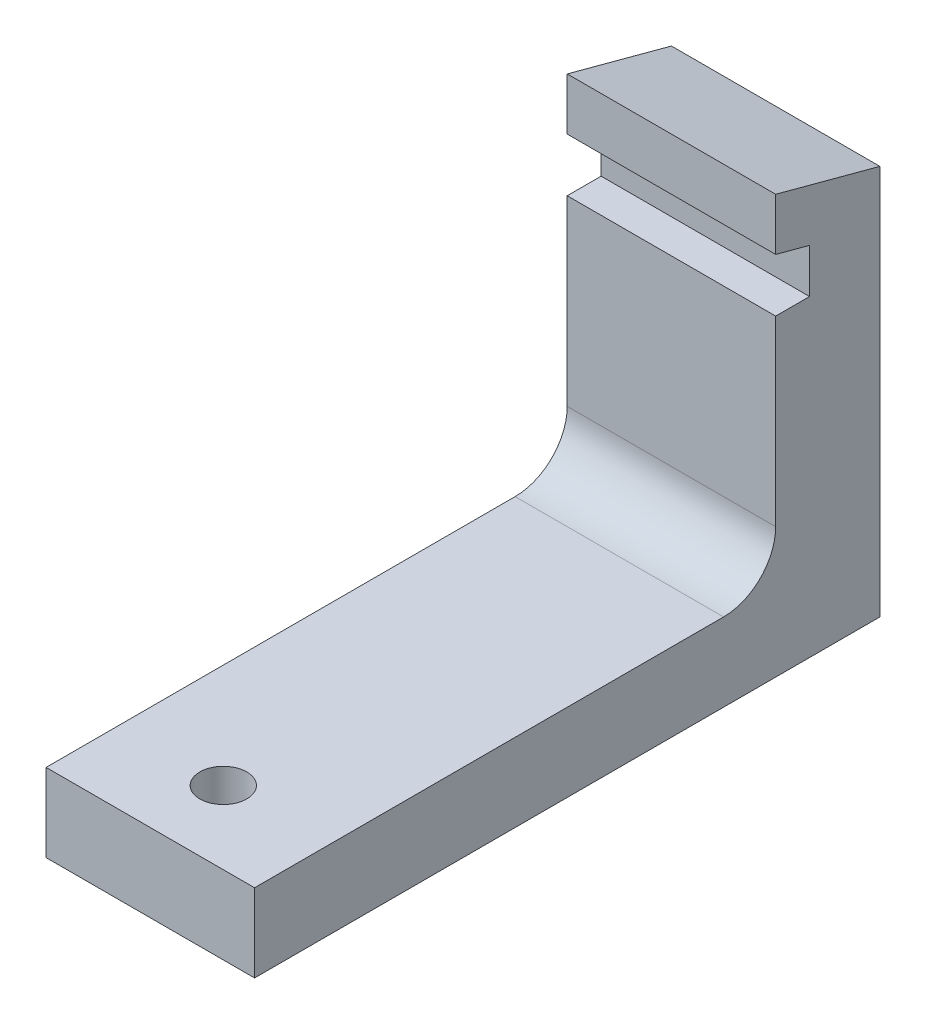
SolidWorks part; units mm, degrees
material "ABS"
ref_plane "Front" through (0, 0, 0) normal (0, 0, 1) x (1, 0, 0)
ref_plane "Top" through (0, 0, 0) normal (0, 1, 0) x (1, 0, 0)
ref_plane "Right" through (0, 0, 0) normal (1, 0, 0) x (0, 0, -1)
ref_axis "X" through (-80.9, 0, 0) along (1, 0, 0)
ref_axis "Y" through (0, -50, 0) along (0, 1, 0)
ref_axis "Z" through (0, 0, -80.9) along (0, 0, 1)
sketch "Sketch1" plane through (0, 0, 0) normal (1, 0, 0) x (0, 0, -1)
  line L0 (0, 3) -> (20, 3)
  line L1 (20, 3) -> (20, 12)
  line L2 (0, 0) -> (24, 0)
  line L3 (0, 3) -> (0, 0)
  line L4 (24, 0) -> (24, 14.9765)
  line L6 (20, 12) -> (21.3, 12)
  line L7 (21.3, 12) -> (21.3, 13.7)
  line L8 (21.3, 13.7) -> (20, 14.0483)
  line L9 (20, 14.0483) -> (20, 16.0483)
  line L10 (20, 16.0483) -> (24, 14.9765)
  dimension "D1" = 15
  dimension "D2" = 1.7
  dimension "D3" = 3
  dimension "D4" = 1.3
  dimension "D5" = 4
  dimension "D6" = 12
  dimension "D7" = 2
  dimension "D8" = 24
extrude "Boss-Extrude1" add sketch "Sketch1" along normal mid plane 8
fillet "Fillet1" radius 2 1 edges at (0, 3, -20)
sketch "Sketch2" plane through (0, 0, 0) normal (0, -1, 0) x (1, 0, 0)
  line L0 (0, -2.8) -> (0, -20.8) construction
  line L1 (0, -20.8) -> (0, -24) construction
  line L2 (4, -24) -> (-4, -24) construction
  circle A0 centre (0, -20.8) radius 0.9
  circle A1 centre (0, -2.8) radius 0.9
  dimension "D3" = 1.8
  dimension "D1" = 3.2
  dimension "D2" = 18
extrude "Cut-Extrude1" cut sketch "Sketch2" against normal blind 4
